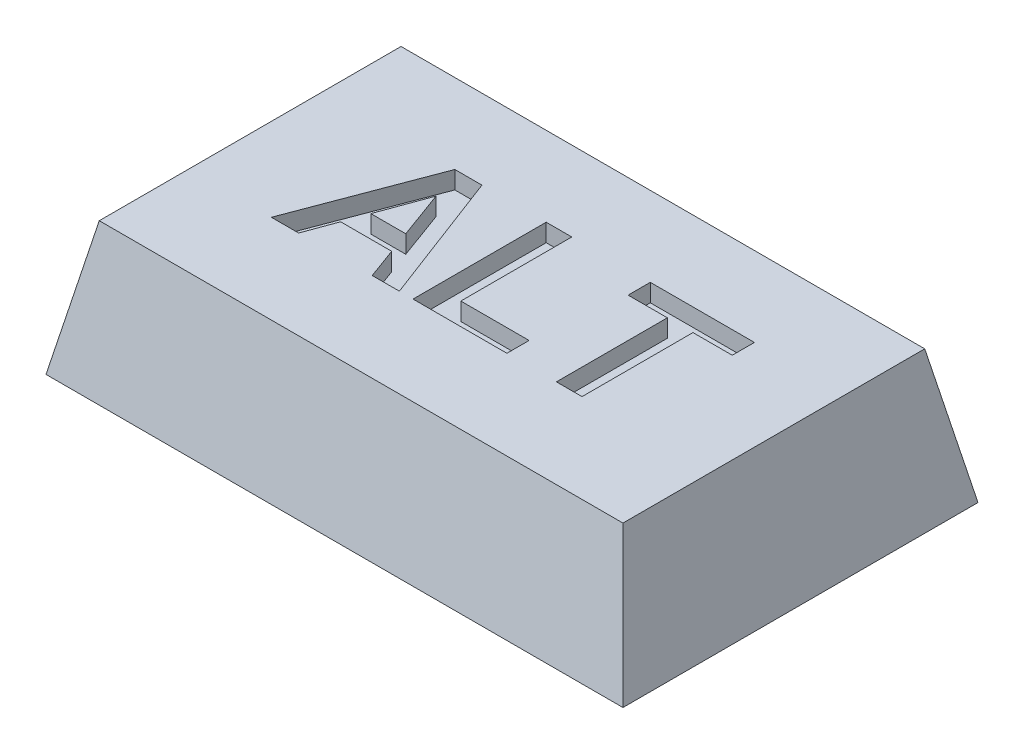
SolidWorks part; units mm, degrees
ref_plane "Front Plane" through (0, 0, 0) normal (0, 0, 1) x (1, 0, 0)
ref_plane "Top Plane" through (0, 0, 0) normal (0, 1, 0) x (1, 0, 0)
ref_plane "Right Plane" through (0, 0, 0) normal (1, 0, 0) x (0, 0, -1)
sketch "Sketch1" plane through (0, 0, 0) normal (0, 1, 0) x (1, 0, 0)
  line L1 (0, 0) -> (13, 0)
  line L2 (0, 0) -> (0, 8)
  line L3 (0, 8) -> (13, 8)
  line L4 (13, 0) -> (13, 8)
  dimension "D1" = 8
  dimension "D2" = 13
extrude "Boss-Extrude1" add sketch "Sketch1" along normal blind 3
sketch "Sketch2" plane through (0, 0, 0) normal (0, 0, 1) x (1, 0, 0)
  line L0 (0, 0) -> (0.6, 3)
  line L1 (0, 3) -> (13, 3) construction
  line L2 (0.6, 3) -> (0, 3)
  line L3 (0, 3) -> (0, 0)
  line L4 (13, 0) -> (12.4, 3)
  line L5 (12.4, 3) -> (13, 3)
  line L6 (13, 3) -> (13, 0)
  dimension "D1" = 0.6
  dimension "D2" = 0.6
extrude "Cut-Extrude1" cut sketch "Sketch2" against normal through all both and the other way through all
sketch "Sketch3" plane through (0, 0, 0) normal (1, 0, 0) x (0, 0, -1)
  line L0 (0, 0) -> (0.6, 3)
  line L1 (8, 3) -> (0, 3) construction
  line L2 (0.6, 3) -> (0, 3)
  line L3 (0, 3) -> (0, 0)
  line L4 (8, 3) -> (7.4, 3)
  line L5 (7.4, 3) -> (8, 0)
  line L6 (8, 3) -> (8, 0)
  dimension "D1" = 0.6
  dimension "D2" = 0.6
extrude "Cut-Extrude2" cut sketch "Sketch3" along normal through all both and the other way through all
sketch "Sketch4" plane through (0, 0, 0) normal (0, -1, 0) x (1, 0, 0)
  line L1 (6.5, 0) -> (6.5, -8) construction
  line L2 (13, -8) -> (0, -8) construction
  line L3 (0, 0) -> (13, 0) construction
  circle A0 centre (6.5, -3.75) radius 1.8
  dimension "D1" = 3.6
  dimension "D2" = 0
  dimension "D3" = 3.75
extrude "Cut-Extrude3" cut sketch "Sketch4" against normal blind 0.8
sketch "Sketch5" plane through (0, 0, 0) normal (0, -1, 0) x (1, 0, 0)
  line L5 (0, 0) -> (13, 0) construction
  line L6 (2.5, -8) -> (10.5, -8)
  line L7 (2.5, -8) -> (2.5, -6.9)
  line L8 (2.5, -6.9) -> (10.5, -6.9)
  line L9 (10.5, -8) -> (10.5, -6.9)
  point P2 (6.5, 0)
  dimension "D1" = 1.1
  dimension "D2" = 4
  dimension "D3" = 4
extrude "Boss-Extrude2" add sketch "Sketch5" along normal blind 2
fillet "Fillet1" radius 4 2 edges at (10.5, -2, -7.45) (2.5, -2, -7.45)
sketch "Sketch6" plane through (0, 3, 0) normal (0, 1, 0) x (1, 0, 0)
  text T0 "ALT" font "Arial" height 3
extrude "Cut-Extrude4" cut sketch "Sketch6" against normal blind 0.4
